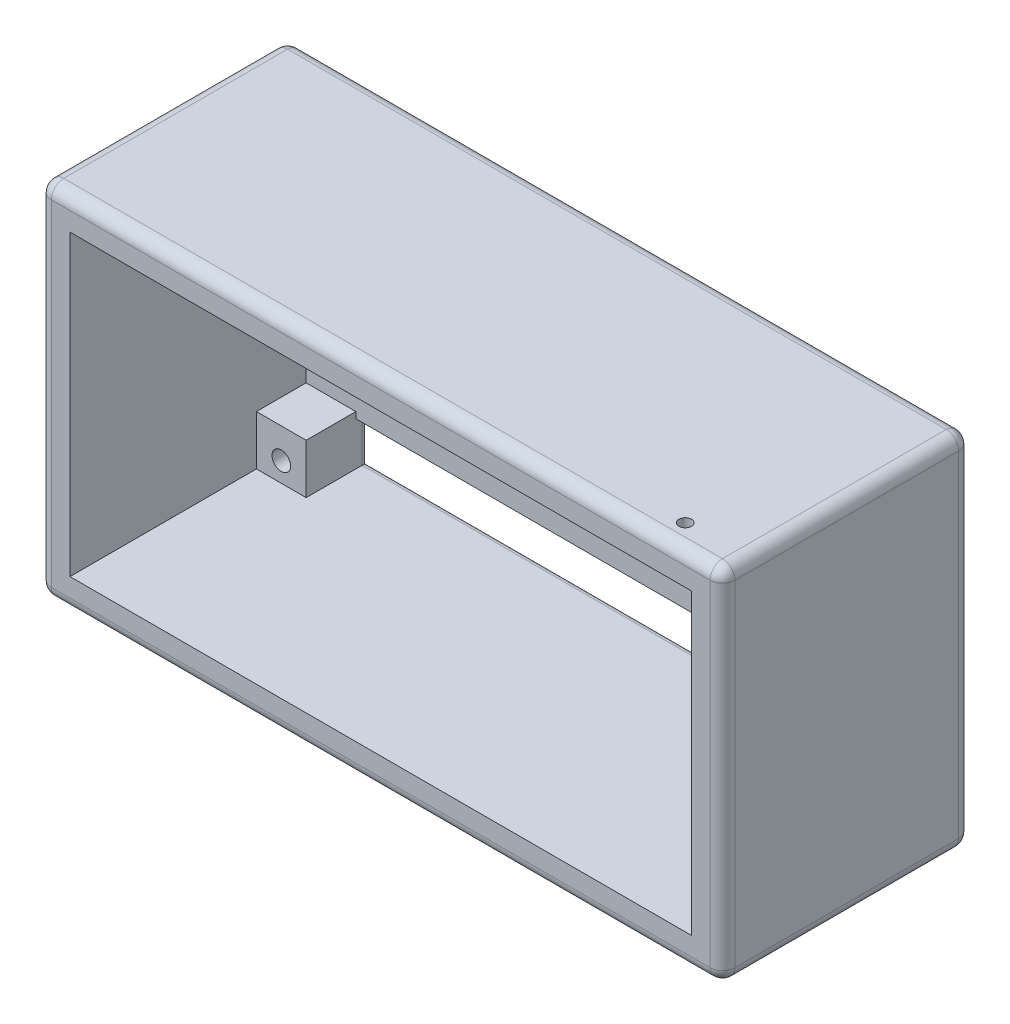
SolidWorks part; units mm, degrees
ref_plane "Спереди" through (0, 0, 0) normal (0, 0, 1) x (1, 0, 0)
ref_plane "Сверху" through (0, 0, 0) normal (0, 1, 0) x (1, 0, 0)
ref_plane "Справа" through (0, 0, 0) normal (1, 0, 0) x (0, 0, -1)
sketch "Эскиз1" plane through (0, 0, 0) normal (0, 0, 1) x (1, 0, 0)
  line L1 (0, 58) -> (110, 58)
  line L2 (0, 58) -> (0, 0)
  line L3 (0, 0) -> (110, 0)
  line L4 (110, 58) -> (110, 0)
  line L5 (13, 12) -> (97, 12)
  line L6 (13, 12) -> (13, 5)
  line L7 (13, 5) -> (97, 5)
  line L8 (97, 12) -> (97, 5)
  circle A0 centre (20.2, 29.6) radius 9.5
  circle A1 centre (89.7, 29.6) radius 9.5
  circle A2 centre (69.2, 29.6) radius 9.5
  circle A3 centre (40.8, 29.6) radius 9.5
  point P13 (0, 0)
  point P14 (0, 0)
  point P15 (97, 0)
  point P16 (0, 0)
  point P17 (97, 0)
  point P18 (13, 0)
  point P19 (0, 0)
  point P20 (0, 0)
  point P25 (0, 0)
  point P26 (0, 0)
  point P27 (0, 0)
  dimension "D3" = 29.6
  dimension "D8" = 19
  dimension "D1" = 58
  dimension "D2" = 110
  dimension "D4" = 20.2
  dimension "D5" = 13
  dimension "D6" = 13
extrude "Бобышка-Вытянуть1" add sketch "Эскиз1" along normal blind 40 contours L5 L8 L3 L4 L1 L2 L6 A3 A2 A1 A0 | A0 | A3 | A2 | A1 | L8 L5 L6 L3 region at (55.0061, 31.4418, 0) region at (55, 8.5, 0) region at (20.2, 29.6, 0) region at (89.7, 29.6, 0) region at (69.2, 29.6, 0) region at (40.8, 29.6, 0)
sketch "Эскиз2" plane through (0, 0, 40) normal (0, 0, 1) x (1, 0, 0)
  line L5 (0, 58) -> (110, 58)
  line L6 (0, 58) -> (0, 0)
  line L7 (0, 0) -> (110, 0)
  line L8 (110, 58) -> (110, 0)
  line L9 (5, 53) -> (105, 53)
  line L10 (5, 53) -> (5, 5)
  line L11 (5, 5) -> (105, 5)
  line L12 (105, 53) -> (105, 5)
  point P10 (0, 0)
  point P11 (0, 0)
  dimension "D1" = 5
  dimension "D2" = 5
  dimension "D3" = 5
  dimension "D4" = 5
extrude "Вырез-Вытянуть1" cut sketch "Эскиз1<4>" along normal blind 2 contours A0 | A3 | A2 | A1 | L5 L8 L7 L6
sketch "Эскиз1<4>" plane through (0, 0, 0) normal (0, 0, 1) x (1, 0, 0) same geometry as "Эскиз1"
extrude "Вырез-Вытянуть4" cut sketch "Эскиз2" against normal blind 30 flip side to cut
sketch "Эскиз3" plane through (0, 58, 0) normal (0, 1, 0) x (1, 0, 0)
  circle A0 centre (100, -36) radius 1
extrude "Вырез-Вытянуть5" cut sketch "Эскиз3" against normal up to next
sketch "Эскиз5" plane through (0, 0, 10) normal (0, 0, 1) x (1, 0, 0)
  line L0 (5, 53) -> (5, 5) construction
  line L1 (5, 53) -> (13, 53)
  line L2 (5, 53) -> (5, 45)
  line L3 (5, 45) -> (13, 45)
  line L4 (13, 53) -> (13, 45)
  line L5 (105, 53) -> (5, 53) construction
  line L6 (0, 58) -> (0, 0) construction
  line L7 (97, 13) -> (105, 13)
  line L8 (97, 13) -> (97, 5)
  line L9 (97, 5) -> (105, 5)
  line L10 (105, 13) -> (105, 5)
  line L19 (5, 13) -> (13, 13)
  line L20 (5, 13) -> (5, 5)
  line L21 (5, 5) -> (13, 5)
  line L22 (13, 13) -> (13, 5)
  line L23 (97, 53) -> (105, 53)
  line L24 (97, 53) -> (97, 45)
  line L25 (97, 45) -> (105, 45)
  line L26 (105, 53) -> (105, 45)
  line L27 (5, 5) -> (105, 5) construction
  line L28 (105, 53) -> (5, 53) construction
  line L29 (105, 5) -> (105, 53) construction
  line L30 (105, 5) -> (105, 53) construction
  line L32 (5, 53) -> (105, 53)
  line L33 (5, 53) -> (5, 5)
  line L34 (5, 5) -> (105, 5)
  line L35 (105, 53) -> (105, 5)
  circle A0 centre (9, 8.15) radius 1.5
  circle A1 centre (101, 49.85) radius 1.5
  circle A2 centre (9, 49.85) radius 1.5
  circle A3 centre (101, 8.15) radius 1.5
  line M17 (5, 53) -> (5, 5)
  line M18 (5, 5) -> (105, 5)
  line M19 (105, 5) -> (105, 53)
  line M20 (105, 53) -> (5, 53)
  dimension "D5" = 41.7
  dimension "D1" = 13
  dimension "D2" = 8
  dimension "D3" = 8
  dimension "D4" = 8
  dimension "D6" = 92
extrude "Вырез-Вытянуть8" cut sketch "Эскиз5" against normal blind 8 contours L25 L24 L4 L3 L19 L22 L8 L7 M20 M17 M18 M19 region at (55, 29, 10)
extrude "Вырез-Вытянуть9" cut sketch "Эскиз5<3>" against normal through all and the other way through all contours A1 | A2 | A0 | A3
sketch "Эскиз5<3>" plane through (0, 0, 10) normal (0, 0, 1) x (1, 0, 0) same geometry as "Эскиз5"
fillet "Скругление1" radius 2 12 edges at (0, 29, 40) (0, 29, 0) (110, 29, 0) (110, 29, 40) (0, 0, 20) (110, 0, 20) (55, 0, 0) (55, 0, 40) (55, 58, 0) (110, 58, 20) (0, 58, 20) (55, 58, 40)
fillet "Скругление3" radius 1 8 edges at (99.2, 29.6, 0) (78.7, 29.6, 0) (50.3, 29.6, 0) (29.7, 29.6, 0) (13, 8.5, 0) (55, 5, 0) (97, 8.5, 0) (55, 12, 0)
